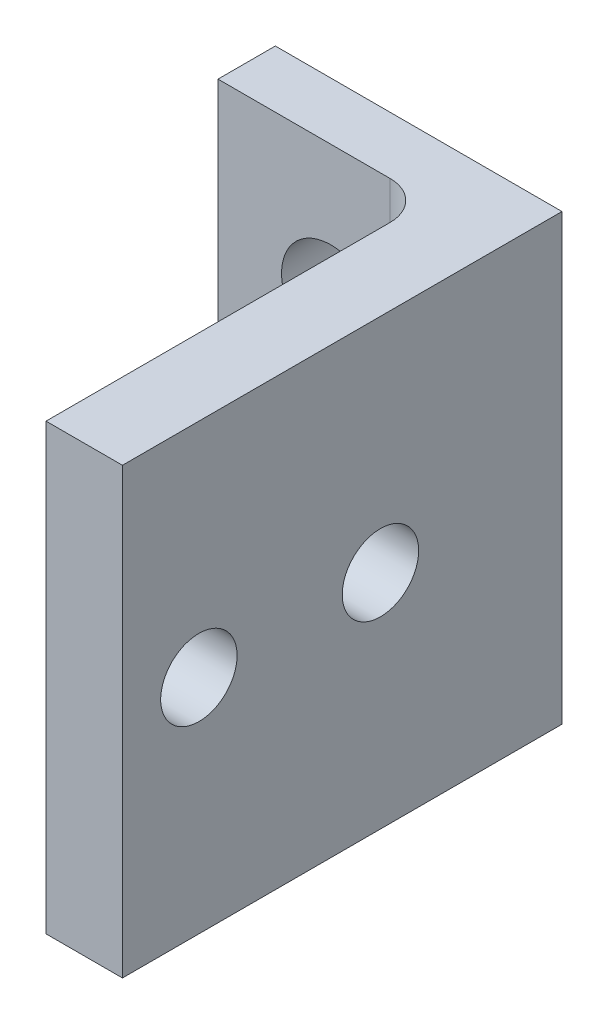
SolidWorks part; units mm, degrees
ref_plane "Front Plane" through (0, 0, 0) normal (0, 0, 1) x (1, 0, 0)
ref_plane "Top Plane" through (0, 0, 0) normal (0, 1, 0) x (1, 0, 0)
ref_plane "Right Plane" through (0, 0, 0) normal (1, 0, 0) x (0, 0, -1)
sketch "Sketch1" plane through (0, 0, 0) normal (0, 0, 1) x (1, 0, 0)
  line L1 (50.33, 18.6565) -> (65.33, 18.6565)
  line L2 (50.33, 18.6565) -> (50.33, -4.58)
  line L3 (50.33, -4.58) -> (65.33, -4.58)
  line L4 (65.33, 18.6565) -> (65.33, -4.58)
  circle A0 centre (56.235, 11.52) radius 2.58
  point P8 (50.8583, 18.6565)
  dimension "D1" = 23.2365
  dimension "D2" = 15
extrude "Boss-Extrude1" add sketch "Sketch1" along normal blind 3
sketch "Sketch2" plane through (0, 0, 3) normal (0, 0, 1) x (1, 0, 0)
  line L0 (65.33, 18.6565) -> (50.33, 18.6565) construction
  line L1 (65.33, -4.58) -> (61.33, -4.58)
  line L2 (65.33, -4.58) -> (65.33, 18.6565)
  line L3 (65.33, 18.6565) -> (61.33, 18.6565)
  line L4 (61.33, -4.58) -> (61.33, 18.6565)
  point P5 (0, 0)
  dimension "D1" = 4
extrude "Boss-Extrude2" add sketch "Sketch2" along normal blind 20
sketch "Sketch3" plane through (65.33, 0, 0) normal (1, 0, 0) x (0, 0, -1)
  line L0 (-23, -4.58) -> (-23, 18.6565) construction
  line L1 (-19, 18.6565) -> (-19, 7.0383) construction
  line L2 (-23, 18.6565) -> (0, 18.6565) construction
  line L3 (-19, 7.0383) -> (-19, -4.58) construction
  line L4 (-23, -4.58) -> (0, -4.58) construction
  circle A0 centre (-19, 7.0383) radius 2
  circle A1 centre (-9.5, 7.0383) radius 2
  dimension "D1" = 4
  dimension "D2" = 4
  dimension "D3" = 9.5
  dimension "D4" = 4
extrude "Cut-Extrude1" cut sketch "Sketch3" against normal blind 4
fillet "Fillet1" radius 2 1 edges at (61.33, 7.0383, 3)
sketch "Sketch4" plane through (0, 0, 3) normal (0, 0, 1) x (1, 0, 0)
  circle A0 centre (56.235, 11.52) radius 4.75
  dimension "D1" = 9.5
extrude "Cut-Extrude2" cut sketch "Sketch4" along normal blind 4
